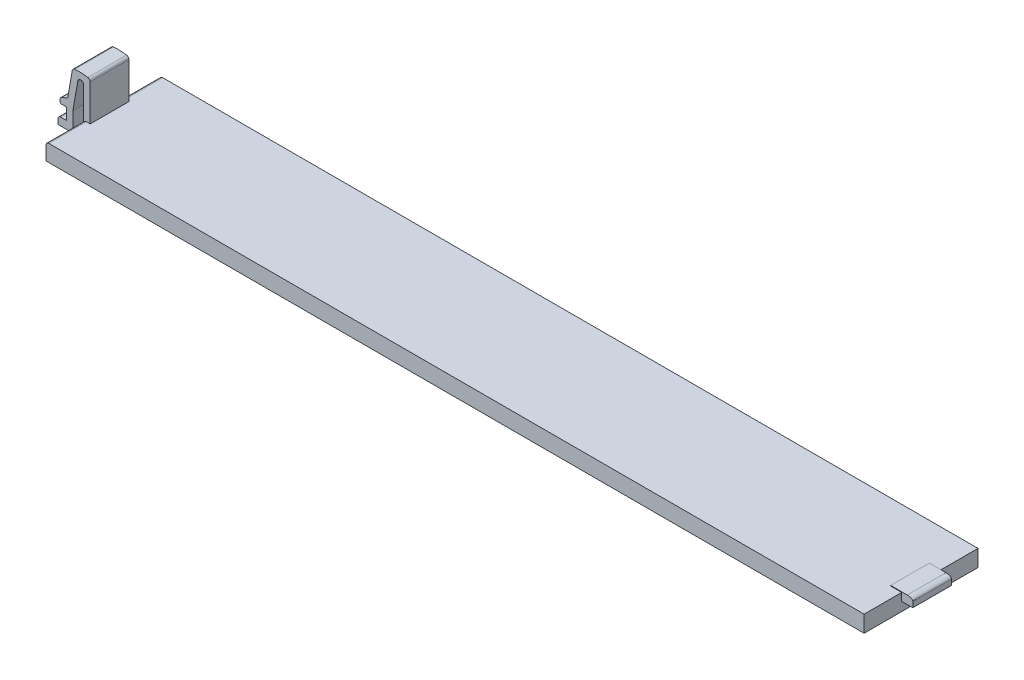
SolidWorks part; units mm, degrees
ref_plane "前视基准面" through (0, 0, 0) normal (0, 0, 1) x (1, 0, 0)
ref_plane "上视基准面" through (0, 0, 0) normal (0, 1, 0) x (1, 0, 0)
ref_plane "右视基准面" through (0, 0, 0) normal (1, 0, 0) x (0, 0, -1)
other "Configuration Table"
sketch "草图1" plane through (0, 0, 0) normal (0, 1, 0) x (1, 0, 0)
  line L1 (-74, 10.3) -> (74, 10.3)
  line L2 (-74, 10.3) -> (-74, -10.3)
  line L3 (-74, -10.3) -> (74, -10.3)
  line L4 (74, 10.3) -> (74, -10.3)
  line L5 (-74, 10.3) -> (74, -10.3) construction
  line L6 (-74, -10.3) -> (74, 10.3) construction
  point P0 (0, 0)
  dimension "D1" = 148
  dimension "D2" = 20.6
extrude "凸台-拉伸1" add sketch "草图1" along normal blind 3
sketch "草图2" plane through (0, 3, 0) normal (0, 1, 0) x (1, 0, 0)
  line L0 (74, -10.3) -> (74, 10.3) construction
  line L1 (72, 3.5) -> (76, 3.5)
  line L2 (72, 3.5) -> (72, -3.5)
  line L3 (72, -3.5) -> (76, -3.5)
  line L4 (76, 3.5) -> (76, -3.5)
  line L5 (74, 0) -> (63.5421, 0) construction
  dimension "D1" = 2
  dimension "D2" = 2
  dimension "D3" = 7
extrude "凸台-拉伸2" add sketch "草图2" along normal blind 1.5 from offset 1.4 offset against normal yes
sketch "草图5" plane through (0, 0, 10.3) normal (0, 0, 1) x (1, 0, 0)
  line L0 (-74, 3) -> (-74, 9)
  line L1 (-74.9616, 9.0287) -> (-75.9365, 3.5)
  line L3 (-76.894, 4.9803) -> (-75.989, 10.1127)
  line L4 (-72.8, 3) -> (-72.8, 10)
  line L5 (-74, 3) -> (74, 3) construction
  line L6 (-74, 0) -> (-75.5, 0) construction
  line L7 (-74, 3) -> (-74, 0) construction
  line L8 (-72.8, 3) -> (-74, 3)
  line L9 (-77.1365, 3.5) -> (-75.9365, 3.5) construction
  line L11 (-75.9365, 3.5) -> (-75.9365, 0)
  line L12 (91.1, 3) -> (-86.9, 3) construction
  line L13 (-77.1365, 3.5) -> (-77.1365, 1.4)
  line L14 (-77.2, 0) -> (-75.9365, 0)
  line L15 (-77.1365, 3.5) -> (-78.2365, 3.5)
  line L16 (-78.2365, 3.5) -> (-78.2365, 4.5)
  line L17 (-78.2365, 4.5) -> (-76.894, 4.9803)
  line L19 (-78.6365, 1.4) -> (-77.1365, 1.4)
  line L20 (-78.6365, 1.4) -> (-78.6365, 0)
  line L21 (-78.6365, 0) -> (-77.2, 0)
  arc A0 (-74.9616, 9.0287) -> (-74, 9) centre (-74.75, 0) cw
  arc A1 (-72.8, 10) -> (-75.989, 10.1127) centre (-74.75, 0) ccw
  dimension "D1" = 1.2
  dimension "D2" = 1.2
  dimension "D3" = 10
  dimension "D4" = 7
  dimension "D5" = 6
  dimension "D6" = 1.5
  dimension "D7" = 2
  dimension "D8" = 1.5
  dimension "D9" = 1
  dimension "D10" = 1.1
  dimension "D11" = 1.2
  dimension "D12" = 1.4
  dimension "D13" = 1.5
  dimension "D14" = 0.5
extrude "凸台-拉伸4" add sketch "草图5" along normal mid plane 7 from surface starting at plane "前视基准面"
fillet "圆角2" radius 0.5 1 edges at (76, 3.1, 0) second distance 1 first distance on face at (76, 2.35, 0)
sketch "草图6" plane through (-78.2365, 0, 0) normal (-1, 0, 0) x (0, 0, 1)
  line L1 (-1.5, 4.9803) -> (1.5, 4.9803)
  line L2 (-1.5, 4.9803) -> (-1.5, 3.5)
  line L3 (-1.5, 3.5) -> (1.5, 3.5)
  line L4 (1.5, 4.9803) -> (1.5, 3.5)
  line L5 (3.5, 3.5) -> (-3.5, 3.5) construction
  line L6 (3.5, 4.5) -> (3.5, 3.5) construction
  line L7 (-3.5, 4.5) -> (-3.5, 3.5) construction
  line L8 (3.5, 4.9803) -> (-3.5, 4.9803) construction
  dimension "D1" = 2
  dimension "D2" = 2
extrude "切除-拉伸1" cut sketch "草图6" against normal up to surface (1.3425 mm away) up to face at (-76.4415, 7.5465, 0)
fillet "圆角3" radius 0.5 9 edges at (-74, 9, 0) (-74.9616, 9.0287, 0) (-72.8, 10, 0) (-75.989, 10.1127, 0) (-78.6365, 1.4, 0) (-78.2365, 4.5, -2.5) (-78.2365, 4.5, 2.5) (-74, 3, -6.9) (-74, 3, 6.9)
fillet "圆角4" radius 0.2 2 edges at (-78.2365, 3.5, 2.5) (-78.2365, 3.5, -2.5)
